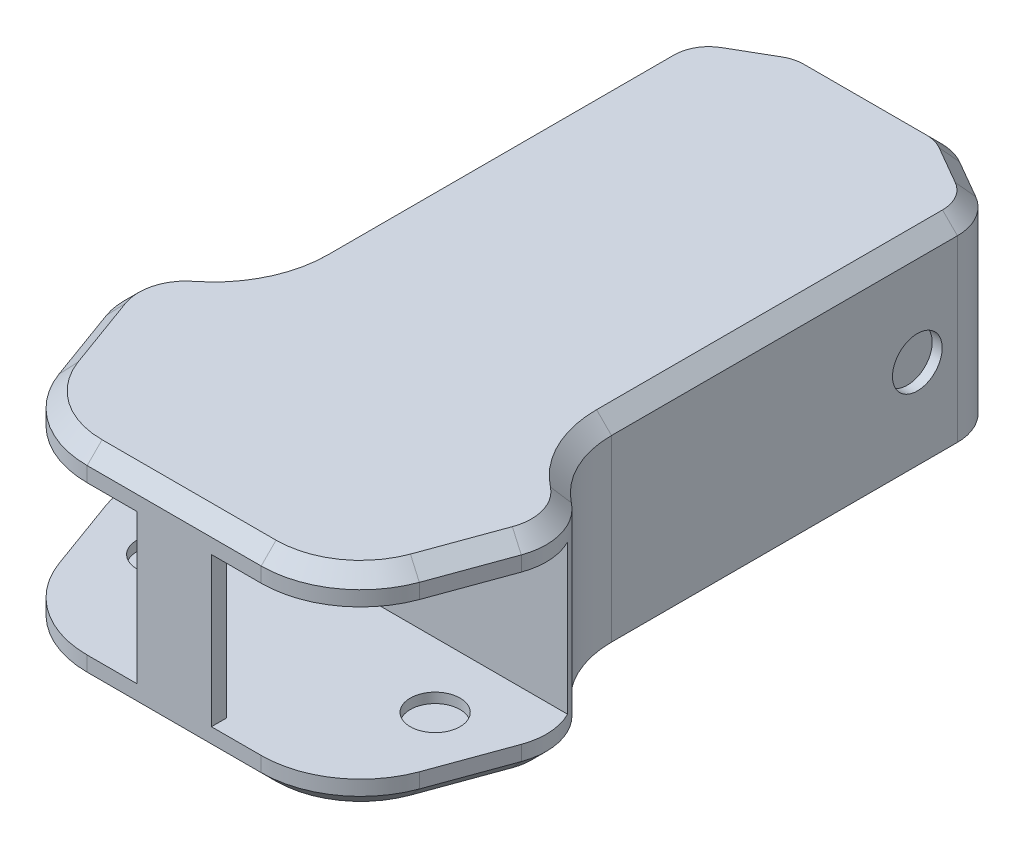
SolidWorks part; units mm, degrees
ref_plane "Front Plane" through (0, 0, 0) normal (0, 0, 1) x (1, 0, 0)
ref_plane "Top Plane" through (0, 0, 0) normal (0, 1, 0) x (1, 0, 0)
ref_plane "Right Plane" through (0, 0, 0) normal (1, 0, 0) x (0, 0, -1)
sketch "Sketch1" plane through (0, 0, 0) normal (0, 1, 0) x (1, 0, 0)
  line L0 (0, -800.5074) -> (0, 39224.8627) construction
  line L1 (12.3205, 0) -> (-12.3205, 0)
  line L2 (-17.3205, -1.3397) -> (-25, -5.7735)
  line L3 (-30, -14.4338) -> (-30, -84.0243)
  line L4 (17.5, -142) -> (-17.5, -142)
  line L5 (-41.7299, -113.9042) -> (-36.2576, -128.9393)
  line L6 (41.7299, -113.9042) -> (36.2576, -128.9393)
  line L7 (30, -14.4338) -> (30, -84.0243)
  line L8 (17.3205, -1.3397) -> (25, -5.7735)
  arc A0 (-17.5, -142) -> (-36.2576, -128.9393) centre (-17.5, -122) cw
  arc A1 (-12.3205, 0) -> (-17.3205, -1.3397) centre (-12.3205, -10) ccw
  arc A2 (-25, -5.7735) -> (-30, -14.4338) centre (-20, -14.4338) ccw
  arc A3 (-37.6823, -99.781) -> (-30, -84.0243) centre (-50, -84.0243) ccw
  arc A4 (-41.7299, -113.9042) -> (-37.6823, -99.781) centre (-29.9837, -109.6289) cw
  arc A5 (41.7299, -113.9042) -> (37.6823, -99.781) centre (29.9837, -109.6289) ccw
  arc A6 (37.6823, -99.781) -> (30, -84.0243) centre (50, -84.0243) cw
  arc A7 (25, -5.7735) -> (30, -14.4338) centre (20, -14.4338) cw
  arc A8 (12.3205, 0) -> (17.3205, -1.3397) centre (12.3205, -10) cw
  arc A9 (17.5, -142) -> (36.2576, -128.9393) centre (17.5, -122) ccw
  point P1 (30, -8.6603)
  point P5 (0, 0)
  point P15 (-42, -114.318)
  point P16 (-42, -106.1852)
  point P17 (-42, -113.8882)
  point P18 (-36.164, -129.1872)
  point P19 (-42, -113.8882)
  point P22 (-15, 0)
  point P25 (-30, -8.6603)
  point P40 (0, -142)
  point P41 (15, 0)
  point P42 (42, -106.1852)
  dimension "D6" = 10
  dimension "D1" = 84
  dimension "D7" = 20
  dimension "D8" = 12.5
  dimension "D9" = 20
  dimension "D2" = 60
  dimension "D3" = 142
  dimension "D4" = 30
  dimension "D5" = 30
  dimension "D10" = 35
  dimension "D11" = 20
  dimension "D12" = 16
extrude "Boss-Extrude1" add sketch "Sketch1" along normal blind 21 and the other way blind 21
sketch "Sketch3" plane through (0, 0, 0) normal (1, 0, 0) x (0, 0, -1)
  line L0 (-142, 15) -> (-104, 15)
  line L1 (-142, -21) -> (-142, 21) construction
  line L2 (-104, 15) -> (-104, -15)
  line L3 (-104, -15) -> (-142, -15)
  line L4 (-142, -15) -> (-142, 15)
  point P4 (-104, 0)
  point P7 (0, 0)
  dimension "D1" = 30
  dimension "D2" = 38
extrude "Cut-Extrude2" cut sketch "Sketch3" against normal through all both and the other way through all
chamfer "Chamfer1" distance 3 angle 45 36 edges at (-42, -21, 106.1852) (-38.9937, -21, 121.4217) (-28.9284, -21, 138.4132) (0, -21, 142) (28.9284, -21, 138.4132) (38.9937, -21, 121.4217) (42, -21, 106.1852) (32.0229, -21, 92.7891) (30, -21, 49.229) (28.6603, -21, 9.4338) (21.1603, -21, 3.5566) (14.9087, -21, 0.3407) (0, -21, 0) (-14.9087, -21, 0.3407) (-21.1603, -21, 3.5566) (-28.6603, -21, 9.4338) (-30, -21, 49.229) (-32.0229, -21, 92.7891) (-30, 21, 49.229) (-28.6603, 21, 9.4338) (-21.1603, 21, 3.5566) (-14.9087, 21, 0.3407) (0, 21, 0) (14.9087, 21, 0.3407) (21.1603, 21, 3.5566) (28.6603, 21, 9.4338) (30, 21, 49.229) (32.0229, 21, 92.7891) (42, 21, 106.1852) (38.9937, 21, 121.4217) (28.9284, 21, 138.4132) (0, 21, 142) (-28.9284, 21, 138.4132) (-38.9937, 21, 121.4217) (-42, 21, 106.1852) (-32.0229, 21, 92.7891)
sketch "Sketch4" plane through (0, -15, 0) normal (0, 1, 0) x (1, 0, 0)
  line L0 (-7.5, -142) -> (7.5, -142)
  line L1 (17.5, -142) -> (-17.5, -142) construction
  line L2 (7.5, -142) -> (7.5, -139)
  line L3 (7.5, -139) -> (-7.5, -139)
  line L4 (-7.5, -139) -> (-7.5, -142)
  point P4 (0, -142)
  point P7 (0, 0)
  dimension "D1" = 15
  dimension "D2" = 3
extrude "Boss-Extrude2" add sketch "Sketch4" along normal up to next
sketch "Sketch5" plane through (0, -15, 0) normal (0, 1, 0) x (1, 0, 0)
  line L0 (0, -1000) -> (0, 49000) construction
  line L2 (17.5, -142) -> (-17.5, -142) construction
  circle A0 centre (-27.5, -117) radius 5
  circle A1 centre (27.5, -117) radius 5
  dimension "D2" = 10
  dimension "D1" = 55
  dimension "D3" = 25
extrude "Cut-Extrude3" cut sketch "Sketch5" against normal blind 2
sketch "Sketch6" plane through (-30, 0, 0) normal (-1, 0, 0) x (0, 0, 1)
  circle A0 centre (22.5, 0) radius 5
  point P2 (0, 0)
  dimension "D1" = 10
  dimension "D2" = 22.5
extrude "Cut-Extrude4" cut sketch "Sketch6" against normal blind 2
mirror "Mirror1" about plane through (0, 0, 0) normal (1, 0, 0) of "Cut-Extrude4"
